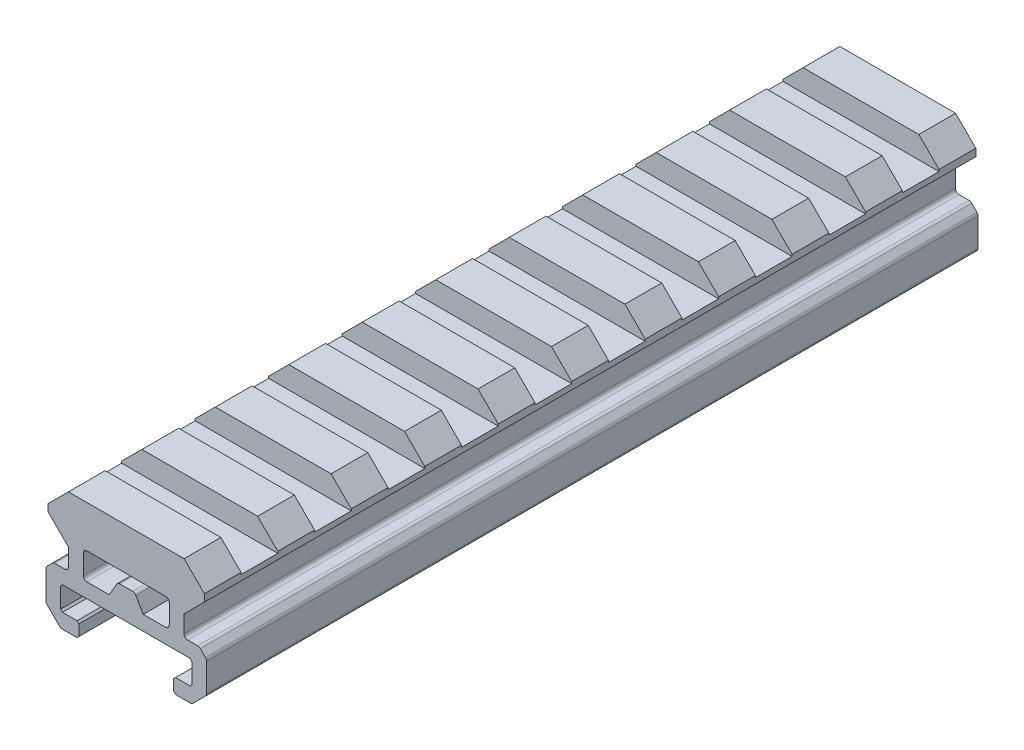
SolidWorks part; units mm, degrees
ref_plane "Front Plane" through (0, 0, 0) normal (0, 0, 1) x (1, 0, 0)
ref_plane "Bottom Plane" through (0, 0, 0) normal (0, 1, 0) x (1, 0, 0)
ref_plane "Right Plane" through (0, 0, 0) normal (1, 0, 0) x (0, 0, -1)
sketch "Sketch1" plane through (0, 0, 0) normal (0, 0, 1) x (1, 0, 0)
  line L0 (7.875, 11.35) -> (10.625, 8.6)
  line L1 (10.625, 7.6) -> (10.625, 8.6)
  line L2 (10.625, 7.6) -> (7.875, 4.85)
  line L3 (7.875, 4.85) -> (7.85, 4.85)
  line L4 (7.85, 4.85) -> (7.85, 2)
  line L5 (7.85, 2) -> (9.925, 2)
  line L6 (10.925, 1) -> (9.925, 2)
  line L7 (10.925, -3.25) -> (10.925, 1)
  line L8 (10.925, -3.25) -> (8.925, -5.25)
  line L9 (8.925, -5.25) -> (6.45, -5.25)
  line L10 (6.45, -5.25) -> (6.45, -3.25)
  line L11 (8.925, -3.25) -> (6.45, -3.25)
  line L14 (8.925, -3.25) -> (8.925, 0)
  line L18 (8.925, 0) -> (-8.925, 0)
  line L19 (-8.925, -3.25) -> (-8.925, 0)
  line L20 (-8.925, -3.25) -> (-6.45, -3.25)
  line L21 (-6.45, -5.25) -> (-6.45, -3.25)
  line L22 (-8.925, -5.25) -> (-6.45, -5.25)
  line L23 (-10.925, -3.25) -> (-8.925, -5.25)
  line L24 (-10.925, -3.25) -> (-10.925, 1)
  line L25 (-10.925, 1) -> (-9.925, 2)
  line L26 (-7.85, 2) -> (-9.925, 2)
  line L27 (-7.85, 4.85) -> (-7.85, 2)
  line L28 (-7.875, 4.85) -> (-7.85, 4.85)
  line L32 (-7.875, 11.35) -> (7.875, 11.35)
  line L33 (-10.625, 7.6) -> (-7.875, 4.85)
  line L34 (-10.625, 7.6) -> (-10.625, 8.6)
  line L35 (-7.875, 11.35) -> (-10.625, 8.6)
  line L36 (0, -1000) -> (0, 49000) construction
  point P0 (-8.925, -1.625)
  point P22 (0, 11.35)
  point P35 (0, 0)
  dimension "D2" = 3.25
  dimension "D3" = 9.35
  dimension "D4" = 15.75
  dimension "D5" = 21.25
  dimension "D6" = 7.85
  dimension "D7" = 8.925
  dimension "D8" = 2
  dimension "D9" = 6.45
  dimension "D10" = 45
  dimension "D11" = 45
  dimension "D12" = 45
  dimension "D13" = 45
  dimension "D14" = 1
  dimension "D15" = 2
  dimension "D16" = 2
  dimension "D17" = 1
  dimension "D18" = 2
  dimension "D19" = 17.85
  dimension "D20" = 2.475
  dimension "D21" = 12.9
extrude "Boss-Extrude1" add sketch "Sketch1" along normal blind 105
sketch "Sketch2" plane through (0, 0, 0) normal (1, 0, 0) x (0, 0, -1)
  line L0 (-995.4377, 11.35) -> (49004.5623, 11.35) construction
  line L16 (5, 11.35) -> (0, 11.35)
  line L17 (5, 11.35) -> (5, 8.35)
  line L18 (5, 8.35) -> (0, 8.35)
  line L23 (0, 11.35) -> (0, 8.35)
  line L81 (-105, 11.35) -> (0, 11.35) construction
  line L92 (-5, 11.35) -> (-10, 11.35)
  line L97 (-5, 11.35) -> (-5, 8.35)
  line L98 (-5, 8.35) -> (-10, 8.35)
  line L99 (-10, 11.35) -> (-10, 8.35)
  line L100 (-15, 11.35) -> (-20, 11.35)
  line L101 (-15, 11.35) -> (-15, 8.35)
  line L102 (-15, 8.35) -> (-20, 8.35)
  line L103 (-20, 11.35) -> (-20, 8.35)
  line L104 (-25, 11.35) -> (-30, 11.35)
  line L105 (-25, 11.35) -> (-25, 8.35)
  line L106 (-25, 8.35) -> (-30, 8.35)
  line L107 (-30, 11.35) -> (-30, 8.35)
  line L108 (-35, 11.35) -> (-40, 11.35)
  line L109 (-35, 11.35) -> (-35, 8.35)
  line L110 (-35, 8.35) -> (-40, 8.35)
  line L111 (-40, 11.35) -> (-40, 8.35)
  line L112 (-45, 11.35) -> (-50, 11.35)
  line L113 (-45, 11.35) -> (-45, 8.35)
  line L114 (-45, 8.35) -> (-50, 8.35)
  line L115 (-50, 11.35) -> (-50, 8.35)
  line L116 (-55, 11.35) -> (-60, 11.35)
  line L117 (-55, 11.35) -> (-55, 8.35)
  line L118 (-55, 8.35) -> (-60, 8.35)
  line L119 (-60, 11.35) -> (-60, 8.35)
  line L120 (-65, 11.35) -> (-70, 11.35)
  line L121 (-65, 11.35) -> (-65, 8.35)
  line L122 (-65, 8.35) -> (-70, 8.35)
  line L123 (-70, 11.35) -> (-70, 8.35)
  line L124 (-75, 11.35) -> (-80, 11.35)
  line L125 (-75, 11.35) -> (-75, 8.35)
  line L126 (-75, 8.35) -> (-80, 8.35)
  line L127 (-80, 11.35) -> (-80, 8.35)
  line L128 (-85, 11.35) -> (-90, 11.35)
  line L129 (-85, 11.35) -> (-85, 8.35)
  line L130 (-85, 8.35) -> (-90, 8.35)
  line L131 (-90, 11.35) -> (-90, 8.35)
  line L132 (-95, 11.35) -> (-100, 11.35)
  line L133 (-95, 11.35) -> (-95, 8.35)
  line L134 (-95, 8.35) -> (-100, 8.35)
  line L135 (-100, 11.35) -> (-100, 8.35)
  line L136 (5, 11.35) -> (-5, 11.35) construction
  dimension "D1" = 5
  dimension "D2" = 3
  dimension "D3" = 10
extrude "Cut-Extrude1" cut sketch "Sketch2" against normal through all both and the other way through all contours L23 | L99 | L103 | L107 | L111 | L115 | L119 | L123 | L127 | L131 | L16 L23 L18 L17 | L92 L99 L98 L97 | L100 L103 L102 L101 | L104 L107 L106 L105 | L108 L111 L110 L109 | L112 L115 L114 L113 | L116 L119 L118 L117 | L120 L123 L122 L121 | L124 L127 L126 L125 | L128 L131 L130 L129 | L132 L135 L134 L133 region at (0, 9.85, -2.5) region at (0, 9.85, 7.5) region at (0, 9.85, 17.5) region at (0, 9.85, 27.5) region at (0, 9.85, 37.5) region at (0, 9.85, 47.5) region at (0, 9.85, 57.5) region at (0, 9.85, 67.5) region at (0, 9.85, 77.5) region at (0, 9.85, 87.5) region at (0, 9.85, 97.5)
sketch "Sketch3" plane through (0, 0, 0) normal (0, 0, 1) x (1, 0, 0)
  line L0 (-7.85, 4.85) -> (-7.85, 2) construction
  line L1 (-10.625, 7.6) -> (-7.875, 4.85) construction
  line L3 (2.3094, 2) -> (1.1547, 4)
  line L4 (1.1547, 4) -> (-1.1547, 4)
  line L5 (-1.1547, 4) -> (-2.3094, 2)
  line L6 (-2.3094, 2) -> (-1.1547, 0)
  line L7 (-1.1547, 0) -> (1.1547, 0)
  line L8 (1.1547, 0) -> (2.3094, 2)
  line L9 (7.85, 2) -> (7.85, 4.85) construction
  line L10 (7.875, 4.85) -> (10.625, 7.6) construction
  line L11 (7.85, 2) -> (7.85, 4.85) construction
  line L12 (7.875, 4.85) -> (10.625, 7.6) construction
  line L13 (-7.85, 4.85) -> (-7.85, 2) construction
  line L14 (-10.625, 7.6) -> (-7.875, 4.85) construction
  line L15 (5.85, 2) -> (5.85, 5.6534)
  line L16 (5.85, 5.6534) -> (6.7966, 6.6) construction
  line L17 (-5.85, 5.6534) -> (-5.85, 2)
  line L18 (-6.7966, 6.6) -> (-5.85, 5.6534) construction
  line L19 (-5.85, 2) -> (5.85, 2)
  line L20 (5.85, 2) -> (5.85, 4.85) construction
  line L21 (-5.85, 4.85) -> (-5.85, 2) construction
  line L22 (-9.2108, 9.0142) -> (-6.4608, 6.2642) construction
  line L23 (6.4608, 6.2642) -> (9.2108, 9.0142) construction
  line L24 (6.7966, 6.6) -> (-6.7966, 6.6) construction
  line L25 (10.625, 7.6) -> (10.625, 8.6) construction
  line L26 (10.625, 8.6) -> (7.875, 11.35) construction
  line L27 (7.875, 11.35) -> (-7.875, 11.35) construction
  line L28 (-7.875, 11.35) -> (-10.625, 8.6) construction
  line L29 (-10.625, 8.6) -> (-10.625, 7.6) construction
  line L30 (10.625, 7.6) -> (10.625, 8.6) construction
  line L31 (10.625, 8.6) -> (7.875, 11.35) construction
  line L32 (7.875, 11.35) -> (-7.875, 11.35) construction
  line L33 (-7.875, 11.35) -> (-10.625, 8.6) construction
  line L34 (-10.625, 8.6) -> (-10.625, 7.6) construction
  line L35 (-5.85, 5.6534) -> (5.85, 5.6534)
  circle A0 centre (0, 2) radius 2 construction
  dimension "D2" = 1
  dimension "D1" = 2
extrude "Cut-Extrude2" cut sketch "Sketch3" along normal up to next contours L35 L17 L19 L5 L4 L3 L15 region at (0, 4.0081, 0)
chamfer "Chamfer1" distance 0.25 angle 45 8 edges at (8.925, 0, 52.5) (8.925, -3.25, 52.5) (6.45, -3.25, 52.5) (6.45, -5.25, 52.5) (-8.925, 0, 52.5) (-8.925, -3.25, 52.5) (-6.45, -3.25, 52.5) (-6.45, -5.25, 52.5)
fillet "Fillet1" radius 0.5 16 edges at (-8.925, -5.25, 52.5) (-10.925, -3.25, 52.5) (8.925, -5.25, 52.5) (10.925, -3.25, 52.5) (10.925, 1, 52.5) (9.925, 2, 52.5) (-10.925, 1, 52.5) (-9.925, 2, 52.5) (-7.85, 2, 52.5) (7.85, 2, 52.5) (-5.85, 5.6534, 52.5) (-5.85, 2, 52.5) (5.85, 2, 52.5) (5.85, 5.6534, 52.5) (-1.1547, 4, 52.5) (1.1547, 4, 52.5)
